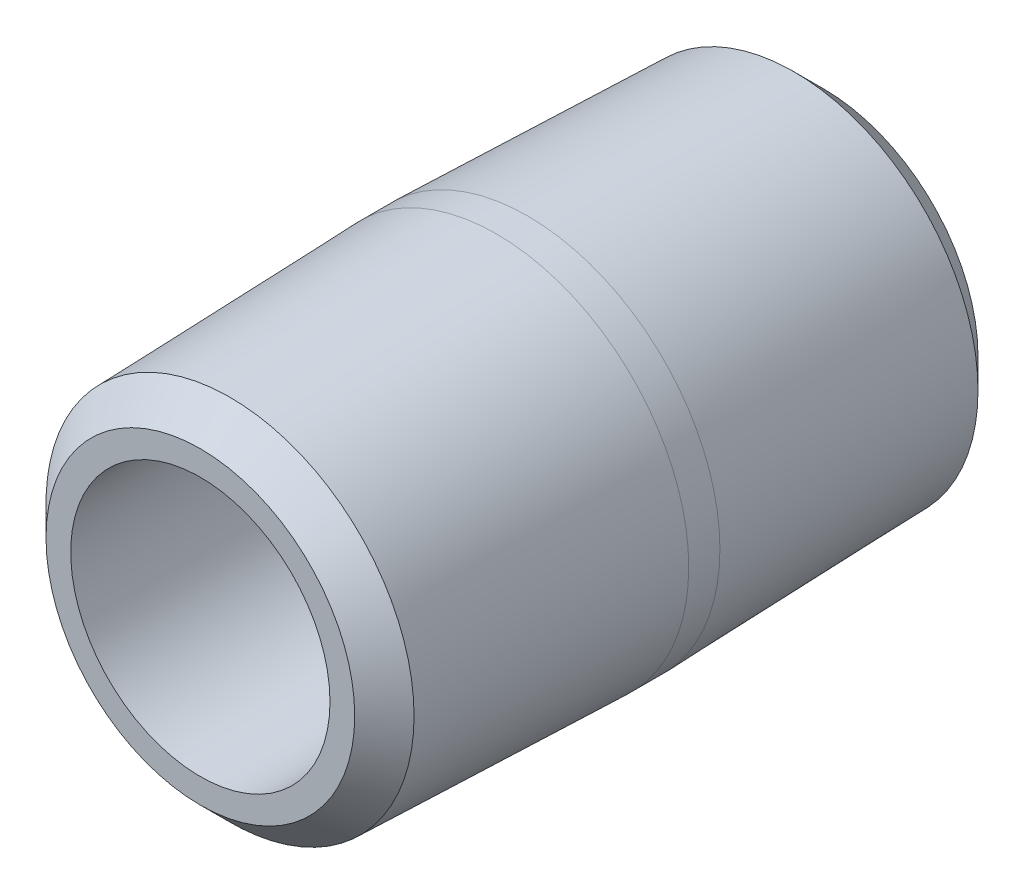
SolidWorks part; units mm, degrees
ref_plane "Front" through (0, 0, 0) normal (0, 0, 1) x (1, 0, 0)
ref_plane "Top" through (0, 0, 0) normal (0, 1, 0) x (1, 0, 0)
ref_plane "Right" through (0, 0, 0) normal (1, 0, 0) x (0, 0, -1)
sketch "Sketch1" plane through (0, 0, 0) normal (1, 0, 0) x (0, 0, -1)
  line L0 (-11.1125, 0) -> (11.1125, 0) construction
  line L1 (-11.1125, 4.6228) -> (-11.1125, 5.5039)
  line L2 (-10.0542, 6.5623) -> (-0.5556, 6.858)
  line L3 (-0.5556, 6.858) -> (0.5556, 6.858)
  line L4 (-0.5556, 6.858) -> (-11.1125, 6.858) construction
  line L5 (-11.1125, 6.858) -> (-11.1125, 5.5039) construction
  line L6 (-10.0542, 6.5623) -> (-11.1125, 5.5039)
  line L7 (-11.1125, 5.5039) -> (-10.0542, 5.5039) construction
  line L8 (-10.0542, 5.5039) -> (-10.0542, 6.5623) construction
  line L9 (-10.0542, 6.5623) -> (-11.1125, 6.5293) construction
  line L10 (-11.1125, 6.5293) -> (-11.6417, 5.6128) construction
  line L11 (-11.6417, 5.6128) -> (-11.8181, 5.6128) construction
  line L12 (-11.8181, 5.6128) -> (-12.5764, 6.9262) construction
  line L13 (-12.5764, 6.9262) -> (-10.8834, 6.9262) construction
  line L14 (-10.8834, 6.9262) -> (-11.1125, 6.5293) construction
  line L15 (-11.3771, 6.071) -> (-12.0826, 6.071) construction
  line L16 (-11.7299, 6.071) -> (-11.7299, 5.6128) construction
  line L17 (-11.7299, 5.8419) -> (-13.141, 5.8419) construction
  line L18 (-11.1125, 4.6228) -> (11.1125, 4.6228)
  line L19 (0, 0) -> (0, 6.858) construction
  line L20 (11.1125, 4.6228) -> (11.1125, 5.5039)
  line L21 (10.0542, 6.5623) -> (11.1125, 5.5039)
  line L22 (10.0542, 6.5623) -> (0.5556, 6.858)
  line L23 (10.0542, -6.5623) -> (0.5556, -6.858) construction
  line L24 (-0.5556, -6.858) -> (0.5556, -6.858) construction
  line L25 (-10.0542, -6.5623) -> (-0.5556, -6.858) construction
  line L26 (-3.3514, -6.771) -> (-3.3514, 0) construction
  line L27 (3.3514, -6.771) -> (3.3514, 0) construction
  point P27 (0, 4.6228)
  dimension "D1" = 1.783
  dimension "D2" = 1.0583
  dimension "D3" = 0.1764
  dimension "D4" = 0.7056
  dimension "D5" = 60
  dimension "D6" = 7.7611
revolve "Revolve1" add sketch "Sketch1" angle 360 about L0
sketch "Sketch2" plane through (0, 0, 0) normal (0, 0, 1) x (1, 0, 0)
  line L0 (-6.858, 0) -> (-4.6228, 0) construction
  line L1 (-4.6228, 0) -> (4.6228, 0) construction
  line L2 (4.6228, 0) -> (6.858, 0) construction
  circle A0 centre (0, 0) radius 4.6228 construction
  circle A1 centre (0, 0) radius 6.858 construction
  circle A2 centre (0, 0) radius 4.6228 construction
  circle A3 centre (0, 0) radius 6.858 construction
sketch "Sketch3" plane through (0, 0, 11.1125) normal (0, 0, 1) x (1, 0, 0)
  circle A0 centre (0, 0) radius 6.5293
curve "Helix/Spiral1"
sketch "Sketch4" [suppressed] plane through (0, 0, 0) normal (1, 0, 0) x (0, 0, -1)
  line L0 (-12.5764, 6.9262) -> (-11.8181, 5.6128)
  line L1 (-11.8181, 5.6128) -> (-11.6417, 5.6128)
  line L2 (-11.6417, 5.6128) -> (-10.8834, 6.9262)
  line L3 (-10.8834, 6.9262) -> (-12.5764, 6.9262)
sweep "Sweep1" [suppressed] add profiles "Sketch4" path "Helix/Spiral1"
sketch "Sketch5" [suppressed] plane through (0, 0, 0) normal (1, 0, 0) x (0, 0, -1)
  line L0 (-11.1125, 0) -> (11.1125, 0) construction
  line L1 (11.1125, -5.4469) -> (-0.5556, -5.4469)
  line L2 (11.1125, -5.4469) -> (11.1125, 5.4469)
  line L3 (11.1125, 5.4469) -> (-0.5556, 5.4469)
  line L4 (-0.5556, -5.4469) -> (-0.5556, 5.4469)
  line L5 (11.1125, -5.4469) -> (-0.5556, 5.4469) construction
  line L6 (11.1125, 5.4469) -> (-0.5556, -5.4469) construction
  line L7 (-0.5556, 6.858) -> (0.5556, 6.858) construction
  line L8 (11.1125, -5.5039) -> (11.1125, 5.5039) construction
  point P0 (5.2784, 0)
  dimension "D1" = 1.4111
extrude "Cut-Extrude1" [suppressed] cut sketch "Sketch5" against normal through all both and the other way through all
ref_axis "Axis1" [suppressed] through (0, 0, 0) along (0, 1, 0)
pattern_circular "CirPattern1" [suppressed] count 2 over 180 about axis through (0, 0, 0) along (0, 1, 0) of bodies 111
combine bodies "Combine1" [suppressed] operation type add bodies to combine 109 111 112
sketch "Sketch6" [suppressed] plane through (0, 0, 0) normal (1, 0, 0) x (0, 0, -1)
  line L0 (-0.5556, 6.858) -> (-6.9056, 4.6228)
  line L1 (-11.1125, 4.6228) -> (11.1125, 4.6228) construction
  line L2 (-6.9056, 4.6228) -> (6.9056, 4.6228)
  line L3 (-0.5556, 6.858) -> (0.5556, 6.858)
  line L4 (-0.5556, 6.858) -> (0.5556, 6.858) construction
  line L5 (0, 6.858) -> (0, 4.6228) construction
  line L6 (0.5556, 6.858) -> (6.9056, 4.6228)
  line L7 (-11.1125, 0) -> (11.1125, 0) construction
  dimension "D1" = 6.35
revolve "Revolve2" [suppressed] add sketch "Sketch6" angle 360 about L7
equation "\"D3@Sketch1\"=\"Pitch@Sketch1\"*.125"
equation "\"D4@Sketch1\"=\"Pitch@Sketch1\"*.5"
equation "\"D2@Sketch1\"=\"Pitch@Sketch1\"*.75"
equation "\"D4@Helix/Spiral1\"=\"Pitch@Sketch1\""
equation "\"D3@Helix/Spiral1\"=\"ThreadLength@Sketch1\"+\"Pitch@Sketch1\""
equation "\"D1@Sketch5\"=\"Pitch@Sketch1\""
equation "\"D1@Sketch6\"=\"Pitch@Sketch1\"*4.5"
equation "\"D6@Sketch1\"=\"Pitch@Sketch1\"*5.5"
